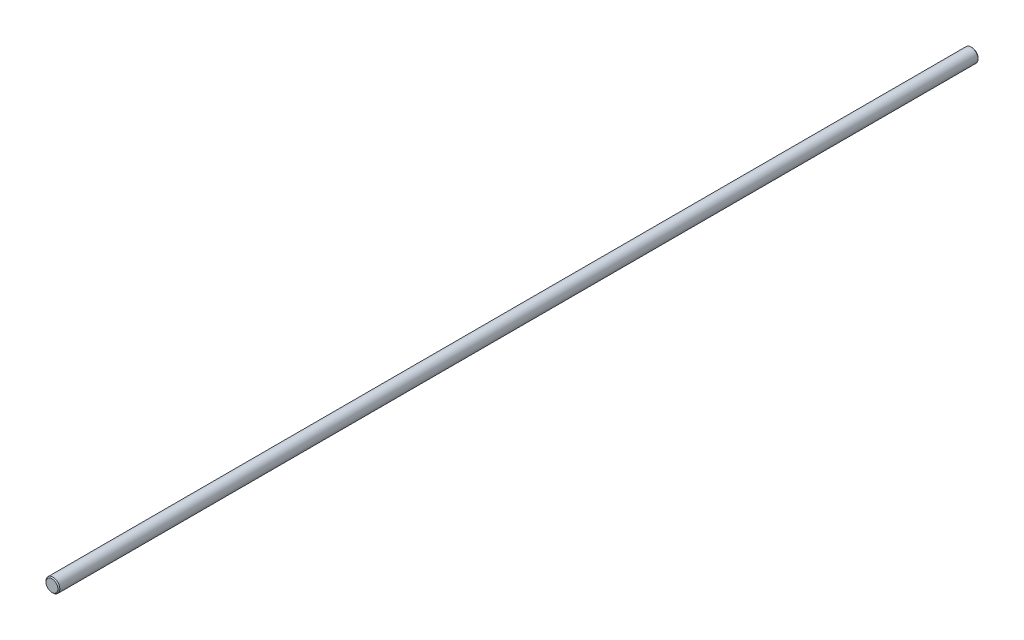
SolidWorks part; units mm, degrees
ref_plane "Front Plane" through (0, 0, 0) normal (0, 0, 1) x (1, 0, 0)
ref_plane "Top Plane" through (0, 0, 0) normal (0, 1, 0) x (1, 0, 0)
ref_plane "Right Plane" through (0, 0, 0) normal (1, 0, 0) x (0, 0, -1)
sketch "Sketch1" plane through (0, 0, 0) normal (0, 0, 1) x (1, 0, 0)
  line L0 (-3, 0) -> (3, 0) construction
  line L5 (0, 3) -> (0, -3) construction
  circle A1 centre (0, 0) radius 3
  point P7 (-3, 0)
  point P8 (3, 0)
  point P12 (0, -3)
  point P13 (0, 3)
  dimension "Diameter" = 6
sketch "Sketch2" plane through (0, 0, 0) normal (1, 0, 0) x (0, 0, -1)
  line L0 (-194, -3) -> (-194, 3) construction
  line L1 (200, -3) -> (-200, -3)
  line L2 (200, -3) -> (200, 3)
  line L3 (200, 3) -> (-200, 3)
  line L4 (-200, -3) -> (-200, 3)
  line L5 (200, -3) -> (-200, 3) construction
  line L6 (200, 3) -> (-200, -3) construction
  line L7 (194, -3) -> (194, 3) construction
  line L8 (-200, 2.58) -> (-199.58, 3) construction
  point P0 (0, 0)
  point P8 (-200, 3)
  point P9 (200, 3)
  point P14 (-194, 3)
  point P15 (-194, -3)
  point P16 (194, 3)
  point P17 (194, -3)
  point P25 (0, -3)
  dimension "Length" = 400
  dimension "D1" = 6
  dimension "D2" = 6
  dimension "Chamfer Typ," = 45
  dimension "D4" = 0.42
sketch "Sketch3" plane through (0, 0, 0) normal (0, 0, 1) x (1, 0, 0)
  circle A0 centre (0, 0) radius 3 construction
  circle A1 centre (0, 0) radius 3
extrude "Boss-Extrude1" add sketch "Sketch3" along normal up to vertex (200 mm away) and the other way up to vertex (200 mm away) up to point (0, 3, 200) other way up to point (0, 3, -200)
chamfer "Chamfer1" distance 0.42 angle 45 2 edges at (3, 0, -200) (3, 0, 200)
equation "\"D1@Sketch2\"=\"Diameter@Sketch1\""
equation "\"D2@Sketch2\"=\"Diameter@Sketch1\""
equation "\"D1@Chamfer1\"=\"Diameter@Sketch1\"*.07"
equation "\"D4@Sketch2\"=\"Diameter@Sketch1\"*.07"
equation "\"D2@Chamfer1\"=\"Chamfer Typ,@Sketch2\""
